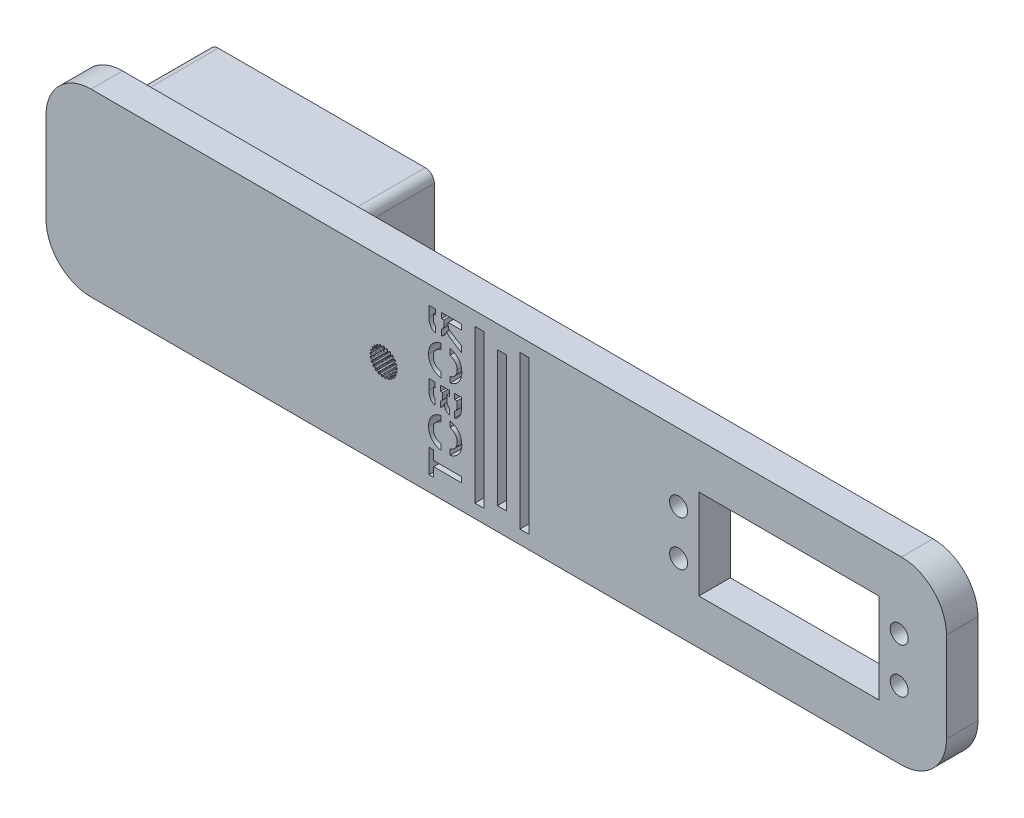
SolidWorks part; units mm, degrees
ref_plane "Alzado" through (0, 0, 0) normal (0, 0, 1) x (1, 0, 0)
ref_plane "Planta" through (0, 0, 0) normal (0, 1, 0) x (1, 0, 0)
ref_plane "Vista lateral" through (0, 0, 0) normal (1, 0, 0) x (0, 0, -1)
sketch "Croquis1" plane through (0, 0, 0) normal (0, 0, 1) x (1, 0, 0)
  line L0 (-64.25, 0) -> (10.75, 0) construction
  line L1 (0, 0) -> (0, -15.2525) construction
  line L2 (135.75, 20) -> (-64.25, 20)
  line L3 (135.75, 20) -> (135.75, -20)
  line L4 (135.75, -20) -> (-64.25, -20)
  line L5 (-64.25, 20) -> (-64.25, -20)
  line L56 (12.6265, 2.2468) -> (12.5286, 2.1823)
  line L57 (12.2759, 2.3659) -> (12.3069, 2.4789)
  line L58 (12.0088, 2.6428) -> (11.93, 2.5561)
  line L59 (11.6396, 2.6711) -> (11.6416, 2.7882)
  line L60 (11.312, 2.8728) -> (11.2572, 2.7692)
  line L61 (10.9474, 2.8084) -> (10.9201, 2.9223)
  line L62 (10.5799, 2.9223) -> (10.5526, 2.8084)
  line L63 (10.2428, 2.7692) -> (10.188, 2.8728)
  line L64 (9.8584, 2.7882) -> (9.8604, 2.6711)
  line L65 (9.57, 2.5561) -> (9.4912, 2.6428)
  line L66 (9.1931, 2.4789) -> (9.2241, 2.3659)
  line L67 (8.9714, 2.1823) -> (8.8735, 2.2468)
  line L68 (8.6255, 2.0138) -> (8.6836, 1.9121)
  line L69 (8.4846, 1.6715) -> (8.3738, 1.7095)
  line L70 (8.1914, 1.4222) -> (8.273, 1.3381)
  line L71 (8.1401, 1.0556) -> (8.0233, 1.0649)
  line L72 (7.9181, 0.7412) -> (8.0181, 0.6801)
  line L73 (7.9596, 0.3733) -> (7.8441, 0.3533)
  line L74 (7.8227, 0.0137) -> (7.9348, -0.0207)
  line L75 (7.9544, -0.3323) -> (7.8475, -0.3805)
  line L76 (7.9113, -0.7147) -> (8.0284, -0.7201)
  line L77 (8.1249, -1.0171) -> (8.0333, -1.0903)
  line L78 (8.1782, -1.3982) -> (8.293, -1.3744)
  line L79 (8.4603, -1.638) -> (8.3898, -1.7317)
  line L80 (8.6068, -1.9939) -> (8.7119, -1.9422)
  line L81 (8.9396, -2.156) -> (8.8946, -2.2642)
  line L82 (9.1699, -2.4642) -> (9.259, -2.3881)
  line L83 (9.5326, -2.5385) -> (9.516, -2.6545)
  line L84 (9.8324, -2.7798) -> (9.8997, -2.6838)
  line L85 (10.2022, -2.7615) -> (10.2149, -2.878)
  line L86 (10.5525, -2.9206) -> (10.5939, -2.811)
  line L87 (10.9061, -2.811) -> (10.9475, -2.9206)
  line L88 (11.2851, -2.878) -> (11.2978, -2.7615)
  line L89 (11.6003, -2.6838) -> (11.6676, -2.7798)
  line L90 (11.984, -2.6545) -> (11.9674, -2.5385)
  line L91 (12.241, -2.3881) -> (12.3301, -2.4642)
  line L92 (12.6054, -2.2642) -> (12.5604, -2.156)
  line L93 (12.7881, -1.9422) -> (12.8932, -1.9939)
  line L94 (13.1102, -1.7317) -> (13.0397, -1.638)
  line L95 (13.207, -1.3744) -> (13.3218, -1.3982)
  line L96 (13.4667, -1.0903) -> (13.3751, -1.0171)
  line L97 (13.4716, -0.7201) -> (13.5887, -0.7147)
  line L98 (13.6525, -0.3805) -> (13.5456, -0.3323)
  line L99 (13.5652, -0.0207) -> (13.6773, 0.0137)
  line L100 (13.6559, 0.3533) -> (13.5404, 0.3733)
  line L101 (13.4819, 0.6801) -> (13.5819, 0.7412)
  line L102 (13.4767, 1.0649) -> (13.3599, 1.0556)
  line L103 (13.227, 1.3381) -> (13.3086, 1.4222)
  line L104 (13.1262, 1.7095) -> (13.0154, 1.6715)
  line L105 (12.8164, 1.9121) -> (12.8745, 2.0138)
  line L106 (12.6265, 2.2468) -> (12.5286, 2.1823)
  line L107 (12.2759, 2.3659) -> (12.3069, 2.4789)
  line L108 (12.0088, 2.6428) -> (11.93, 2.5561)
  line L109 (11.6396, 2.6711) -> (11.6416, 2.7882)
  line L110 (11.312, 2.8728) -> (11.2572, 2.7692)
  line L111 (10.9474, 2.8084) -> (10.9201, 2.9223)
  line L112 (10.5799, 2.9223) -> (10.5526, 2.8084)
  line L113 (10.2428, 2.7692) -> (10.188, 2.8728)
  line L114 (9.8584, 2.7882) -> (9.8604, 2.6711)
  line L115 (9.57, 2.5561) -> (9.4912, 2.6428)
  line L116 (9.1931, 2.4789) -> (9.2241, 2.3659)
  line L117 (8.9714, 2.1823) -> (8.8735, 2.2468)
  line L118 (8.6255, 2.0138) -> (8.6836, 1.9121)
  line L119 (8.4846, 1.6715) -> (8.3738, 1.7095)
  line L120 (8.1914, 1.4222) -> (8.273, 1.3381)
  line L121 (8.1401, 1.0556) -> (8.0233, 1.0649)
  line L122 (7.9181, 0.7412) -> (8.0181, 0.6801)
  line L123 (7.9596, 0.3733) -> (7.8441, 0.3533)
  line L124 (7.8227, 0.0137) -> (7.9348, -0.0207)
  line L125 (7.9544, -0.3323) -> (7.8475, -0.3805)
  line L126 (7.9113, -0.7147) -> (8.0284, -0.7201)
  line L127 (8.1249, -1.0171) -> (8.0333, -1.0903)
  line L128 (8.1782, -1.3982) -> (8.293, -1.3744)
  line L129 (8.4603, -1.638) -> (8.3898, -1.7317)
  line L130 (8.6068, -1.9939) -> (8.7119, -1.9422)
  line L131 (8.9396, -2.156) -> (8.8946, -2.2642)
  line L132 (9.1699, -2.4642) -> (9.259, -2.3881)
  line L133 (9.5326, -2.5385) -> (9.516, -2.6545)
  line L134 (9.8324, -2.7798) -> (9.8997, -2.6838)
  line L135 (10.2022, -2.7615) -> (10.2149, -2.878)
  line L136 (10.5525, -2.9206) -> (10.5939, -2.811)
  line L137 (10.9061, -2.811) -> (10.9475, -2.9206)
  line L138 (11.2851, -2.878) -> (11.2978, -2.7615)
  line L139 (11.6003, -2.6838) -> (11.6676, -2.7798)
  line L140 (11.984, -2.6545) -> (11.9674, -2.5385)
  line L141 (12.241, -2.3881) -> (12.3301, -2.4642)
  line L142 (12.6054, -2.2642) -> (12.5604, -2.156)
  line L143 (12.7881, -1.9422) -> (12.8932, -1.9939)
  line L144 (13.1102, -1.7317) -> (13.0397, -1.638)
  line L145 (13.207, -1.3744) -> (13.3218, -1.3982)
  line L146 (13.4667, -1.0903) -> (13.3751, -1.0171)
  line L147 (13.4716, -0.7201) -> (13.5887, -0.7147)
  line L148 (13.6525, -0.3805) -> (13.5456, -0.3323)
  line L149 (13.5652, -0.0207) -> (13.6773, 0.0137)
  line L150 (13.6559, 0.3533) -> (13.5404, 0.3733)
  line L151 (13.4819, 0.6801) -> (13.5819, 0.7412)
  line L152 (13.4767, 1.0649) -> (13.3599, 1.0556)
  line L153 (13.227, 1.3381) -> (13.3086, 1.4222)
  line L154 (13.1262, 1.7095) -> (13.0154, 1.6715)
  line L155 (12.8164, 1.9121) -> (12.8745, 2.0138)
  arc A53 (12.8931, 2.1702) -> (12.7813, 2.2751) centre (10.75, 0) ccw
  arc A54 (12.2759, 2.3659) -> (12.5286, 2.1823) centre (12.4487, 2.3381) ccw
  arc A55 (12.2861, 2.635) -> (12.1517, 2.7088) centre (10.75, 0) ccw
  arc A56 (11.6396, 2.6711) -> (11.93, 2.5561) centre (11.8139, 2.6871) ccw
  arc A57 (11.5825, 2.9342) -> (11.434, 2.9723) centre (10.75, 0) ccw
  arc A58 (10.9474, 2.8084) -> (11.2572, 2.7692) centre (11.1122, 2.8672) ccw
  arc A59 (10.8267, 3.049) -> (10.6733, 3.049) centre (10.75, 0) ccw
  arc A60 (10.2428, 2.7692) -> (10.5526, 2.8084) centre (10.3878, 2.8672) ccw
  arc A61 (10.066, 2.9723) -> (9.9175, 2.9342) centre (10.75, 0) ccw
  arc A62 (9.57, 2.5561) -> (9.8604, 2.6711) centre (9.6861, 2.6871) ccw
  arc A63 (9.3483, 2.7088) -> (9.2139, 2.635) centre (10.75, 0) ccw
  arc A64 (8.9714, 2.1823) -> (9.2241, 2.3659) centre (9.0513, 2.3381) ccw
  arc A65 (8.7187, 2.2751) -> (8.6069, 2.1702) centre (10.75, 0) ccw
  arc A66 (8.4846, 1.6715) -> (8.6836, 1.9121) centre (8.5232, 1.8422) ccw
  arc A67 (8.2167, 1.6985) -> (8.1345, 1.569) centre (10.75, 0) ccw
  arc A68 (8.1401, 1.0556) -> (8.273, 1.3381) centre (8.135, 1.2305) ccw
  arc A69 (7.8739, 1.0151) -> (7.8265, 0.8693) centre (10.75, 0) ccw
  arc A70 (7.9596, 0.3733) -> (8.0181, 0.6801) centre (7.9112, 0.5415) ccw
  arc A71 (7.7118, 0.268) -> (7.7022, 0.1149) centre (10.75, 0) ccw
  arc A72 (7.9544, -0.3323) -> (7.9348, -0.0207) centre (7.8657, -0.1815) ccw
  arc A73 (7.7406, -0.496) -> (7.7693, -0.6466) centre (10.75, 0) ccw
  arc A74 (8.1249, -1.0171) -> (8.0284, -0.7201) centre (8.0014, -0.8931) ccw
  arc A75 (7.9585, -1.2289) -> (8.0238, -1.3676) centre (10.75, 0) ccw
  arc A76 (8.4603, -1.638) -> (8.293, -1.3744) centre (8.3099, -1.5485) ccw
  arc A77 (8.3518, -1.8845) -> (8.4495, -2.0026) centre (10.75, 0) ccw
  arc A78 (8.9396, -2.156) -> (8.7119, -1.9422) centre (8.7717, -2.1067) ccw
  arc A79 (8.8958, -2.4217) -> (9.0198, -2.5118) centre (10.75, 0) ccw
  arc A80 (9.5326, -2.5385) -> (9.259, -2.3881) centre (9.3577, -2.5325) ccw
  arc A81 (9.5563, -2.8067) -> (9.6988, -2.8631) centre (10.75, 0) ccw
  arc A82 (10.2022, -2.7615) -> (9.8997, -2.6838) centre (10.0313, -2.7992) ccw
  arc A83 (10.2918, -3.0154) -> (10.4439, -3.0346) centre (10.75, 0) ccw
  arc A84 (10.9061, -2.811) -> (10.5939, -2.811) centre (10.75, -2.89) ccw
  arc A85 (11.0561, -3.0346) -> (11.2082, -3.0154) centre (10.75, 0) ccw
  arc A86 (11.6003, -2.6838) -> (11.2978, -2.7615) centre (11.4687, -2.7992) ccw
  arc A87 (11.8012, -2.8631) -> (11.9437, -2.8067) centre (10.75, 0) ccw
  arc A88 (12.241, -2.3881) -> (11.9674, -2.5385) centre (12.1423, -2.5325) ccw
  arc A89 (12.4802, -2.5118) -> (12.6042, -2.4217) centre (10.75, 0) ccw
  arc A90 (12.7881, -1.9422) -> (12.5604, -2.156) centre (12.7283, -2.1067) ccw
  arc A91 (13.0505, -2.0026) -> (13.1482, -1.8845) centre (10.75, 0) ccw
  arc A92 (13.207, -1.3744) -> (13.0397, -1.638) centre (13.1901, -1.5485) ccw
  arc A93 (13.4762, -1.3676) -> (13.5415, -1.2289) centre (10.75, 0) ccw
  arc A94 (13.4716, -0.7201) -> (13.3751, -1.0171) centre (13.4986, -0.8931) ccw
  arc A95 (13.7307, -0.6466) -> (13.7594, -0.496) centre (10.75, 0) ccw
  arc A96 (13.5652, -0.0207) -> (13.5456, -0.3323) centre (13.6343, -0.1815) ccw
  arc A97 (13.7978, 0.1149) -> (13.7882, 0.268) centre (10.75, 0) ccw
  arc A98 (13.4819, 0.6801) -> (13.5404, 0.3733) centre (13.5888, 0.5415) ccw
  arc A99 (13.6735, 0.8693) -> (13.6261, 1.0151) centre (10.75, 0) ccw
  arc A100 (13.227, 1.3381) -> (13.3599, 1.0556) centre (13.365, 1.2305) ccw
  arc A101 (13.3655, 1.569) -> (13.2833, 1.6985) centre (10.75, 0) ccw
  arc A102 (12.8164, 1.9121) -> (13.0154, 1.6715) centre (12.9768, 1.8422) ccw
  arc A103 (12.8931, 2.1702) -> (12.7813, 2.2751) centre (10.75, 0) ccw
  arc A104 (12.2759, 2.3659) -> (12.5286, 2.1823) centre (12.4487, 2.3381) ccw
  arc A105 (12.2861, 2.635) -> (12.1517, 2.7088) centre (10.75, 0) ccw
  arc A106 (11.6396, 2.6711) -> (11.93, 2.5561) centre (11.8139, 2.6871) ccw
  arc A107 (11.5825, 2.9342) -> (11.434, 2.9723) centre (10.75, 0) ccw
  arc A108 (10.9474, 2.8084) -> (11.2572, 2.7692) centre (11.1122, 2.8672) ccw
  arc A109 (10.8267, 3.049) -> (10.6733, 3.049) centre (10.75, 0) ccw
  arc A110 (10.2428, 2.7692) -> (10.5526, 2.8084) centre (10.3878, 2.8672) ccw
  arc A111 (10.066, 2.9723) -> (9.9175, 2.9342) centre (10.75, 0) ccw
  arc A112 (9.57, 2.5561) -> (9.8604, 2.6711) centre (9.6861, 2.6871) ccw
  arc A113 (9.3483, 2.7088) -> (9.2139, 2.635) centre (10.75, 0) ccw
  arc A114 (8.9714, 2.1823) -> (9.2241, 2.3659) centre (9.0513, 2.3381) ccw
  arc A115 (8.7187, 2.2751) -> (8.6069, 2.1702) centre (10.75, 0) ccw
  arc A116 (8.4846, 1.6715) -> (8.6836, 1.9121) centre (8.5232, 1.8422) ccw
  arc A117 (8.2167, 1.6985) -> (8.1345, 1.569) centre (10.75, 0) ccw
  arc A118 (8.1401, 1.0556) -> (8.273, 1.3381) centre (8.135, 1.2305) ccw
  arc A119 (7.8739, 1.0151) -> (7.8265, 0.8693) centre (10.75, 0) ccw
  arc A120 (7.9596, 0.3733) -> (8.0181, 0.6801) centre (7.9112, 0.5415) ccw
  arc A121 (7.7118, 0.268) -> (7.7022, 0.1149) centre (10.75, 0) ccw
  arc A122 (7.9544, -0.3323) -> (7.9348, -0.0207) centre (7.8657, -0.1815) ccw
  arc A123 (7.7406, -0.496) -> (7.7693, -0.6466) centre (10.75, 0) ccw
  arc A124 (8.1249, -1.0171) -> (8.0284, -0.7201) centre (8.0014, -0.8931) ccw
  arc A125 (7.9585, -1.2289) -> (8.0238, -1.3676) centre (10.75, 0) ccw
  arc A126 (8.4603, -1.638) -> (8.293, -1.3744) centre (8.3099, -1.5485) ccw
  arc A127 (8.3518, -1.8845) -> (8.4495, -2.0026) centre (10.75, 0) ccw
  arc A128 (8.9396, -2.156) -> (8.7119, -1.9422) centre (8.7717, -2.1067) ccw
  arc A129 (8.8958, -2.4217) -> (9.0198, -2.5118) centre (10.75, 0) ccw
  arc A130 (9.5326, -2.5385) -> (9.259, -2.3881) centre (9.3577, -2.5325) ccw
  arc A131 (9.5563, -2.8067) -> (9.6988, -2.8631) centre (10.75, 0) ccw
  arc A132 (10.2022, -2.7615) -> (9.8997, -2.6838) centre (10.0313, -2.7992) ccw
  arc A133 (10.2918, -3.0154) -> (10.4439, -3.0346) centre (10.75, 0) ccw
  arc A134 (10.9061, -2.811) -> (10.5939, -2.811) centre (10.75, -2.89) ccw
  arc A135 (11.0561, -3.0346) -> (11.2082, -3.0154) centre (10.75, 0) ccw
  arc A136 (11.6003, -2.6838) -> (11.2978, -2.7615) centre (11.4687, -2.7992) ccw
  arc A137 (11.8012, -2.8631) -> (11.9437, -2.8067) centre (10.75, 0) ccw
  arc A138 (12.241, -2.3881) -> (11.9674, -2.5385) centre (12.1423, -2.5325) ccw
  arc A139 (12.4802, -2.5118) -> (12.6042, -2.4217) centre (10.75, 0) ccw
  arc A140 (12.7881, -1.9422) -> (12.5604, -2.156) centre (12.7283, -2.1067) ccw
  arc A141 (13.0505, -2.0026) -> (13.1482, -1.8845) centre (10.75, 0) ccw
  arc A142 (13.207, -1.3744) -> (13.0397, -1.638) centre (13.1901, -1.5485) ccw
  arc A143 (13.4762, -1.3676) -> (13.5415, -1.2289) centre (10.75, 0) ccw
  arc A144 (13.4716, -0.7201) -> (13.3751, -1.0171) centre (13.4986, -0.8931) ccw
  arc A145 (13.7307, -0.6466) -> (13.7594, -0.496) centre (10.75, 0) ccw
  arc A146 (13.5652, -0.0207) -> (13.5456, -0.3323) centre (13.6343, -0.1815) ccw
  arc A147 (13.7978, 0.1149) -> (13.7882, 0.268) centre (10.75, 0) ccw
  arc A148 (13.4819, 0.6801) -> (13.5404, 0.3733) centre (13.5888, 0.5415) ccw
  arc A149 (13.6735, 0.8693) -> (13.6261, 1.0151) centre (10.75, 0) ccw
  arc A150 (13.227, 1.3381) -> (13.3599, 1.0556) centre (13.365, 1.2305) ccw
  arc A151 (13.3655, 1.569) -> (13.2833, 1.6985) centre (10.75, 0) ccw
  arc A152 (12.8164, 1.9121) -> (13.0154, 1.6715) centre (12.9768, 1.8422) ccw
  spline S50 degree 3 poles (5991.9772, -495.1912) (-77.9359, 29.7028) (12.0665, -1.5466) (12.9076, 2.1011) (12.9095, 2.115) (12.8341, 3.4331) (-11.0318, 17.2816) (-3713.5828, -4698.8555) knots -68.19884 -68.19884 -68.19884 -68.19884 0.5 0.5 0.75 0.75 23.694066 23.694066 23.694066 23.694066 only from (12.8745, 2.0138) to (12.8931, 2.1702)
  spline S51 degree 3 poles (-4350.7805, -4114.6425) (28.1487, -21.0181) (14.0631, 2.2949) (12.7252, 2.2881) (12.7115, 2.2853) (9.1534, 1.2271) (43.9396, -86.0291) (-459.254, 5983.3688) knots -22.897234 -22.897234 -22.897234 -22.897234 0.25 0.25 0.5 0.5 68.630064 68.630064 68.630064 68.630064 only from (12.7813, 2.2751) to (12.6265, 2.2468)
  spline S52 degree 3 poles (5927.215, 1007.8369) (-82.5365, 6.7143) (12.4097, -1.1707) (12.3173, 2.5717) (12.3157, 2.5856) (11.9148, 3.8436) (-14.6453, 11.3217) (-2428.0182, -5477.4362) knots -68.19884 -68.19884 -68.19884 -68.19884 0.5 0.5 0.75 0.75 23.694066 23.694066 23.694066 23.694066 only from (12.3069, 2.4789) to (12.2861, 2.635)
  spline S53 degree 3 poles (-3190.485, -5070.042) (32.8291, -16.0309) (13.3883, 3.0468) (12.0941, 2.7074) (12.0816, 2.7013) (8.8984, 0.7915) (64.2914, -75.0724) (-1932.4913, 5678.5051) knots -22.897234 -22.897234 -22.897234 -22.897234 0.25 0.25 0.5 0.5 68.630064 68.630064 68.630064 68.630064 only from (12.1517, 2.7088) to (12.0088, 2.6428)
  spline S54 degree 3 poles (5490.6996, 2447.5389) (-81.2755, -16.696) (12.6487, -0.7211) (11.6285, 2.8806) (11.6235, 2.8938) (10.9224, 4.0125) (-16.663, 4.6505) (-989.2168, -5911.8495) knots -68.19884 -68.19884 -68.19884 -68.19884 0.5 0.5 0.75 0.75 23.694066 23.694066 23.694066 23.694066 only from (11.6416, 2.7882) to (11.5825, 2.9342)
  spline S55 degree 3 poles (-1829.0442, -5706.8721) (36.1221, -10.0364) (12.5477, 3.6072) (11.3786, 2.9566) (11.368, 2.9476) (8.7597, 0.3062) (81.2791, -59.3987) (-3283.6276, 5016.8399) knots -22.897234 -22.897234 -22.897234 -22.897234 0.25 0.25 0.5 0.5 68.630064 68.630064 68.630064 68.630064 only from (11.434, 2.9723) to (11.312, 2.8728)
  spline S56 degree 3 poles (4709.8587, 3733.453) (-74.2322, -39.0573) (12.7684, -0.2263) (10.8845, 3.0086) (10.8764, 3.0201) (9.9191, 3.9293) (-16.9583, -2.3129) (512.4161, -5974.7995) knots -68.19884 -68.19884 -68.19884 -68.19884 0.5 0.5 0.75 0.75 23.694066 23.694066 23.694066 23.694066 only from (10.9201, 2.9223) to (10.8267, 3.049)
  spline S57 degree 3 poles (-352.0023, -5985.1184) (37.821, -3.4113) (11.5942, 3.9409) (10.6236, 3.0201) (10.6155, 3.0087) (8.7461, -0.1984) (93.8351, -39.9927) (-4427.766, 4039.9483) knots -22.897234 -22.897234 -22.897234 -22.897234 0.25 0.25 0.5 0.5 68.630064 68.630064 68.630064 68.630064 only from (10.6733, 3.049) to (10.5799, 2.9223)
  spline S58 degree 3 poles (3633.7556, 4784.7805) (-61.8492, -58.9645) (12.7613, 0.2828) (10.1321, 2.9476) (10.1214, 2.9566) (8.968, 3.5992) (-15.5126, -9.1311) (1982.5276, -5662.3309) knots -68.19884 -68.19884 -68.19884 -68.19884 0.5 0.5 0.75 0.75 23.694066 23.694066 23.694066 23.694066 only from (10.188, 2.8728) to (10.066, 2.9723)
  spline S59 degree 3 poles (1147.8327, -5887.2977) (37.8188, 3.4281) (10.5876, 4.0271) (9.8765, 2.8938) (9.8715, 2.8807) (8.8584, -0.6905) (101.1706, -18.0738) (-5293.0161, 2809.2118) knots -22.897234 -22.897234 -22.897234 -22.897234 0.25 0.25 0.5 0.5 68.630064 68.630064 68.630064 68.630064 only from (9.9175, 2.9342) to (9.8584, 2.7882)
  spline S60 degree 3 poles (2330.0056, 5535.4627) (-44.9045, -75.1667) (12.6278, 0.7741) (9.4185, 2.7013) (9.4058, 2.7074) (8.1289, 3.043) (-12.4167, -15.3754) (3328.745, -4994.0772) knots -68.19884 -68.19884 -68.19884 -68.19884 0.5 0.5 0.75 0.75 23.694066 23.694066 23.694066 23.694066 only from (9.4912, 2.6428) to (9.3483, 2.7088)
  spline S61 degree 3 poles (2576.2205, -5419.5565) (36.1159, 10.0522) (9.5912, 3.8602) (9.1843, 2.5856) (9.1827, 2.5717) (9.0895, -1.1392) (102.8246, 4.9807) (-5825.0111, 1401.9623) knots -22.897234 -22.897234 -22.897234 -22.897234 0.25 0.25 0.5 0.5 68.630064 68.630064 68.630064 68.630064 only from (9.2139, 2.635) to (9.1931, 2.4789)
  spline S62 degree 3 poles (880.5284, 5938.3314) (-24.4628, -86.6459) (12.3763, 1.2167) (8.7885, 2.2853) (8.7748, 2.2881) (7.4545, 2.2955) (-7.8652, -20.6537) (4466.4806, -4012.0273) knots -68.19884 -68.19884 -68.19884 -68.19884 0.5 0.5 0.75 0.75 23.694066 23.694066 23.694066 23.694066 only from (8.8735, 2.2468) to (8.7187, 2.2751)
  spline S63 degree 3 poles (3843.4104, -4611.2846) (32.8191, 16.0446) (8.6676, 3.4507) (8.5904, 2.115) (8.5924, 2.1012) (9.425, -1.5164) (98.6933, 27.7223) (-5990.3238, -93.3777) knots -22.897234 -22.897234 -22.897234 -22.897234 0.25 0.25 0.5 0.5 68.630064 68.630064 68.630064 68.630064 only from (8.6069, 2.1702) to (8.6255, 2.0138)
  spline S64 degree 3 poles (-623.6003, 5968.0728) (-1.8086, -92.6808) (12.0226, 1.583) (8.2818, 1.7257) (8.2678, 1.725) (6.9872, 1.4038) (-2.144, -24.6343) (5324.2462, -2777.8869) knots -68.19884 -68.19884 -68.19884 -68.19884 0.5 0.5 0.75 0.75 23.694066 23.694066 23.694066 23.694066 only from (8.3738, 1.7095) to (8.2167, 1.6985)
  spline S65 degree 3 poles (4869.7802, -3513.2687) (28.1356, 21.0289) (7.8749, 2.8244) (8.1323, 1.5115) (8.1376, 1.4986) (9.8438, -1.7982) (89.0362, 48.7219) (-5778.5669, -1582.8504) knots -22.897234 -22.897234 -22.897234 -22.897234 0.25 0.25 0.5 0.5 68.630064 68.630064 68.630064 68.630064 only from (8.1345, 1.569) to (8.1914, 1.4222)
  spline S66 degree 3 poles (-2087.8703, 5622.8184) (21.6348, -92.8922) (11.5889, 1.8497) (7.9302, 1.0577) (7.9168, 1.0535) (6.7563, 0.424) (4.3874, -27.0669) (5848.1454, -1369.2017) knots -68.19884 -68.19884 -68.19884 -68.19884 0.5 0.5 0.75 0.75 23.694066 23.694066 23.694066 23.694066 only from (8.0233, 1.0649) to (7.8739, 1.0151)
  spline S67 degree 3 poles (5590.8392, -2194.5012) (22.3597, 24.6919) (7.2628, 2.0207) (7.8387, 0.813) (7.847, 0.8018) (10.3194, -1.9671) (74.46, 66.6602) (-5203.046, -2972.8669) knots -22.897234 -22.897234 -22.897234 -22.897234 0.25 0.25 0.5 0.5 68.630064 68.630064 68.630064 68.630064 only from (7.8265, 0.8693) to (7.9181, 0.7412)
  spline S68 degree 3 poles (-3420.2764, 4924.2615) (44.3942, -87.2669) (11.1026, 2.0002) (7.7558, 0.3232) (7.7438, 0.3158) (6.7763, -0.5826) (11.3186, -27.7989) (6005.2595, 125.5155) knots -68.19884 -68.19884 -68.19884 -68.19884 0.5 0.5 0.75 0.75 23.694066 23.694066 23.694066 23.694066 only from (7.8441, 0.3533) to (7.7118, 0.268)
  spline S69 degree 3 poles (5961.2807, -737.8452) (15.8544, 26.8034) (6.8699, 1.09) (7.7279, 0.0635) (7.7388, 0.0547) (10.8222, -2.0124) (55.8807, 80.41) (-4299.9231, -4176.0871) knots -22.897234 -22.897234 -22.897234 -22.897234 0.25 0.25 0.5 0.5 68.630064 68.630064 68.630064 68.630064 only from (7.7022, 0.1149) to (7.8227, 0.0137)
  spline S70 degree 3 poles (-4537.0984, 3916.2952) (65.0396, -76.1583) (10.5941, 2.0251) (7.7695, -0.4316) (7.7597, -0.4417) (7.046, -1.5525) (18.214, -26.7841) (5785.7165, 1612.3461) knots -68.19884 -68.19884 -68.19884 -68.19884 0.5 0.5 0.75 0.75 23.694066 23.694066 23.694066 23.694066 only from (7.8475, -0.3805) to (7.7406, -0.496)
  spline S71 degree 3 poles (5957.8285, 765.1724) (9.0283, 27.2307) (6.7207, 0.0908) (7.8071, -0.6901) (7.8198, -0.6959) (11.3204, -1.9312) (34.4657, 89.1073) (-3125.9447, -5116.9085) knots -22.897234 -22.897234 -22.897234 -22.897234 0.25 0.25 0.5 0.5 68.630064 68.630064 68.630064 68.630064 only from (7.7693, -0.6466) to (7.9113, -0.7147)
  spline S72 degree 3 poles (-5368.1624, 2662.2537) (82.2738, -60.2644) (10.0953, 1.9227) (7.9704, -1.1593) (7.9635, -1.1715) (7.5485, -2.4248) (24.6405, -24.0864) (5203.3112, 2997.867) knots -68.19884 -68.19884 -68.19884 -68.19884 0.5 0.5 0.75 0.75 23.694066 23.694066 23.694066 23.694066 only from (8.0333, -1.0903) to (7.9585, -1.2289)
  spline S73 degree 3 poles (5580.6995, 2220.1114) (2.3104, 25.947) (6.8247, -0.9141) (8.0712, -1.4003) (8.0849, -1.4027) (11.7827, -1.7287) (11.5605, 92.2057) (-1754.8763, -5736.2156) knots -22.897234 -22.897234 -22.897234 -22.897234 0.25 0.25 0.5 0.5 68.630064 68.630064 68.630064 68.630064 only from (8.0238, -1.3676) to (8.1782, -1.3982)
  spline S74 degree 3 poles (-5861.2496, 1240.933) (95.0139, -40.5839) (9.6378, 1.6994) (8.3461, -1.8141) (8.3424, -1.8277) (8.2521, -3.1449) (30.1941, -19.8753) (4294.6381, 4195.021) knots -68.19884 -68.19884 -68.19884 -68.19884 0.5 0.5 0.75 0.75 23.694066 23.694066 23.694066 23.694066 only from (8.3898, -1.7317) to (8.3518, -1.8845)
  spline S75 degree 3 poles (4853.59, 3535.5526) (-3.8772, 23.033) (7.1754, -1.8616) (8.5036, -2.0225) (8.5175, -2.0214) (12.1802, -1.4176) (-11.3955, 89.5105) (-272.8671, -5995.0953) knots -22.897234 -22.897234 -22.897234 -22.897234 0.25 0.25 0.5 0.5 68.630064 68.630064 68.630064 68.630064 only from (8.4495, -2.0026) to (8.6068, -1.9939)
  spline S76 degree 3 poles (-5985.3774, -258.3601) (102.4594, -18.3533) (9.2501, 1.3695) (8.8727, -2.3549) (8.8726, -2.369) (9.1127, -3.6673) (34.526, -14.4153) (3116.7926, 5128.5863) knots -68.19884 -68.19884 -68.19884 -68.19884 0.5 0.5 0.75 0.75 23.694066 23.694066 23.694066 23.694066 only from (8.8946, -2.2642) to (8.8958, -2.4217)
  spline S77 degree 3 poles (3822.1871, 4628.8421) (-9.1458, 18.6717) (7.7506, -2.6921) (9.0771, -2.5176) (9.0903, -2.5131) (12.4878, -1.0174) (-32.9602, 81.191) (1226.9628, -5877.2811) knots -22.897234 -22.897234 -22.897234 -22.897234 0.25 0.25 0.5 0.5 68.630064 68.630064 68.630064 68.630064 only from (9.0198, -2.5118) to (9.1699, -2.4642)
  spline S78 degree 3 poles (-5732.7465, -1741.4195) (104.1424, 5.0305) (8.9566, 0.9534) (9.5174, -2.7478) (9.5207, -2.7615) (10.0761, -3.9592) (37.364, -8.0496) (1743.783, 5739.9037) knots -68.19884 -68.19884 -68.19884 -68.19884 0.5 0.5 0.75 0.75 23.694066 23.694066 23.694066 23.694066 only from (9.516, -2.6545) to (9.5563, -2.8067)
  spline S79 degree 3 poles (2551.2976, 5431.2843) (-13.1642, 13.1373) (8.5143, -3.3534) (9.7558, -2.8545) (9.7675, -2.8469) (12.6862, -0.5532) (-51.7783, 67.7699) (2650.3736, -5390.1756) knots -22.897234 -22.897234 -22.897234 -22.897234 0.25 0.25 0.5 0.5 68.630064 68.630064 68.630064 68.630064 only from (9.6988, -2.8631) to (9.8324, -2.7798)
  spline S80 degree 3 poles (-5119.2306, -3115.0591) (99.9573, 28.0982) (8.7759, 0.4775) (10.2394, -2.968) (10.2461, -2.9804) (11.0819, -4.0024) (38.5297, -1.1781) (261.8806, 5990.5619) knots -68.19884 -68.19884 -68.19884 -68.19884 0.5 0.5 0.75 0.75 23.694066 23.694066 23.694066 23.694066 only from (10.2149, -2.878) to (10.2918, -3.0154)
  spline S81 degree 3 poles (1120.7761, 5892.459) (-15.68, 6.7773) (9.4185, -3.804) (10.4969, -3.0121) (10.5063, -3.0018) (12.763, -0.0543) (-66.6675, 50.0906) (3907.9272, -4564.3856) knots -22.897234 -22.897234 -22.897234 -22.897234 0.25 0.25 0.5 0.5 68.630064 68.630064 68.630064 68.630064 only from (10.4439, -3.0346) to (10.5525, -2.9206)
  spline S82 degree 3 poles (-4183.3791, -4292.9681) (90.1669, 49.4004) (8.7191, -0.0285) (10.9936, -3.0018) (11.0031, -3.0121) (12.0668, -3.7942) (37.95, 5.7675) (-1235.8013, 5864.811) knots -68.19884 -68.19884 -68.19884 -68.19884 0.5 0.5 0.75 0.75 23.694066 23.694066 23.694066 23.694066 only from (10.9475, -2.9206) to (11.0561, -3.0346)
  spline S83 degree 3 poles (-379.4924, 5983.3889) (-16.5351, -0.0085) (10.4064, -4.0157) (11.2539, -2.9804) (11.2605, -2.9681) (12.7132, 0.448) (-76.6924, 29.264) (4920.6067, -3451.7985) knots -22.897234 -22.897234 -22.897234 -22.897234 0.25 0.25 0.5 0.5 68.630064 68.630064 68.630064 68.630064 only from (11.2082, -3.0154) to (11.2851, -2.878)
  spline S84 degree 3 poles (-2983.9951, -5201.1341) (75.3865, 67.5986) (8.79, -0.5326) (11.7325, -2.8469) (11.7442, -2.8545) (12.969, -3.3475) (35.6611, 12.3506) (-2655.1578, 5370.5525) knots -68.19884 -68.19884 -68.19884 -68.19884 0.5 0.5 0.75 0.75 23.694066 23.694066 23.694066 23.694066 only from (11.6676, -2.7798) to (11.8012, -2.8631)
  spline S85 degree 3 poles (-1855.2405, 5698.3604) (-15.6757, -6.7937) (11.4158, -3.9749) (11.9793, -2.7615) (11.9826, -2.7479) (12.5401, 0.9221) (-81.2229, 6.5986) (5624.7819, -2122.3222) knots -22.897234 -22.897234 -22.897234 -22.897234 0.25 0.25 0.5 0.5 68.630064 68.630064 68.630064 68.630064 only from (11.9437, -2.8067) to (11.984, -2.6545)
  spline S86 degree 3 poles (-1596.4402, -5782.4937) (56.5447, 81.5493) (8.9841, -1.0033) (12.4096, -2.5131) (12.4229, -2.5176) (13.7318, -2.6905) (31.807, 18.1578) (-3907.0055, 4538.8424) knots -68.19884 -68.19884 -68.19884 -68.19884 0.5 0.5 0.75 0.75 23.694066 23.694066 23.694066 23.694066 only from (12.3301, -2.4642) to (12.4802, -2.5118)
  spline S87 degree 3 poles (-3213.7416, 5055.283) (-13.156, -13.1521) (12.3835, -3.6845) (12.6274, -2.369) (12.6273, -2.355) (12.2546, 1.3384) (-79.9744, -16.4814) (5976.2069, -659.4926) knots -22.897234 -22.897234 -22.897234 -22.897234 0.25 0.25 0.5 0.5 68.630064 68.630064 68.630064 68.630064 only from (12.6042, -2.4217) to (12.6054, -2.2642)
  spline S88 degree 3 poles (-107.8996, -6000.518) (34.8255, 90.376) (9.2891, -1.411) (12.9824, -2.0214) (12.9964, -2.0225) (14.3072, -1.8644) (26.6298, 22.824) (-4912.6862, 3421.9401) knots -68.19884 -68.19884 -68.19884 -68.19884 0.5 0.5 0.75 0.75 23.694066 23.694066 23.694066 23.694066 only from (12.8932, -1.9939) to (13.0505, -2.0026)
  spline S89 degree 3 poles (-4369.636, 4094.5635) (-9.1342, -18.6841) (13.2484, -3.1625) (13.1576, -1.8277) (13.154, -1.8142) (11.8745, 1.6705) (-73.0253, -38.5259) (5952.8002, 844.7754) knots -22.897234 -22.897234 -22.897234 -22.897234 0.25 0.25 0.5 0.5 68.630064 68.630064 68.630064 68.630064 only from (13.1482, -1.8845) to (13.1102, -1.7317)
  spline S90 degree 3 poles (1388.0961, -5841.5076) (11.5936, 93.524) (9.6859, -1.73) (13.415, -1.4027) (13.4288, -1.4003) (14.6591, -0.9212) (20.4548, 26.0561) (-5609.0093, 2090.0248) knots -68.19884 -68.19884 -68.19884 -68.19884 0.5 0.5 0.75 0.75 23.694066 23.694066 23.694066 23.694066 only from (13.3218, -1.3982) to (13.4762, -1.3676)
  spline S91 degree 3 poles (-5250.2946, 2876.5676) (-3.8629, -23.0421) (13.9564, -2.4418) (13.5365, -1.1715) (13.5296, -1.1593) (11.4237, 1.8976) (-60.8124, -58.1496) (5556.0327, 2295.963) knots -22.897234 -22.897234 -22.897234 -22.897234 0.25 0.25 0.5 0.5 68.630064 68.630064 68.630064 68.630064 only from (13.5415, -1.2289) to (13.4667, -1.0903)
  spline S92 degree 3 poles (2797.5481, -5315.4539) (-11.6914, 90.7955) (10.1495, -1.9403) (13.6801, -0.6959) (13.6929, -0.6901) (14.7654, 0.0799) (13.67, 27.6509) (-5952.2223, 626.7855) knots -68.19884 -68.19884 -68.19884 -68.19884 0.5 0.5 0.75 0.75 23.694066 23.694066 23.694066 23.694066 only from (13.5887, -0.7147) to (13.7307, -0.6466)
  spline S93 degree 3 poles (-5800.3825, 1477.8263) (2.3265, -25.9523) (14.4629, -1.5677) (13.7403, -0.4417) (13.7306, -0.4317) (10.9306, 2.0056) (-44.1029, -74.1196) (4810.8347, 3602.8868) knots -22.897234 -22.897234 -22.897234 -22.897234 0.25 0.25 0.5 0.5 68.630064 68.630064 68.630064 68.630064 only from (13.7594, -0.496) to (13.6525, -0.3805)
  spline S94 degree 3 poles (4031.8953, -4455.4106) (-33.5663, 82.3621) (10.6509, -2.0286) (13.7611, 0.0546) (13.7721, 0.0635) (14.6194, 1.076) (6.7018, 27.5084) (-5920.7597, -875.837) knots -68.19884 -68.19884 -68.19884 -68.19884 0.5 0.5 0.75 0.75 23.694066 23.694066 23.694066 23.694066 only from (13.6773, 0.0137) to (13.7978, 0.1149)
  spline S95 degree 3 poles (-5985.3355, -13.7722) (9.0452, -27.2318) (14.7362, -0.5951) (13.7562, 0.3158) (13.7443, 0.3231) (10.4262, 1.9875) (-23.9468, -85.4323) (3764.0296, 4683.428) knots -22.897234 -22.897234 -22.897234 -22.897234 0.25 0.25 0.5 0.5 68.630064 68.630064 68.630064 68.630064 only from (13.7882, 0.268) to (13.6559, 0.3533)
  spline S96 degree 3 poles (5013.5792, -3315.4175) (-52.6566, 68.7535) (11.1585, -1.9895) (13.6529, 0.8018) (13.6613, 0.813) (14.2302, 2.0045) (-0.0121, 25.6375) (-5516.5986, -2323.4274) knots -68.19884 -68.19884 -68.19884 -68.19884 0.5 0.5 0.75 0.75 23.694066 23.694066 23.694066 23.694066 only from (13.5819, 0.7412) to (13.6735, 0.8693)
  spline S97 degree 3 poles (-5793.5325, -1504.5054) (15.871, -26.8002) (14.7589, 0.4149) (13.5832, 1.0535) (13.5699, 1.0577) (9.9421, 1.8445) (-1.6106, -91.377) (2481.3923, 5469.6922) knots -22.897234 -22.897234 -22.897234 -22.897234 0.25 0.25 0.5 0.5 68.630064 68.630064 68.630064 68.630064 only from (13.6261, 1.0151) to (13.4767, 1.0649)
  spline S98 degree 3 poles (5680.917, -1967.1046) (-67.7629, 50.8249) (11.6405, -1.8254) (13.3624, 1.4985) (13.3677, 1.5115) (13.6224, 2.807) (-6.0498, 22.1556) (-4765.1339, -3625.0284) knots -68.19884 -68.19884 -68.19884 -68.19884 0.5 0.5 0.75 0.75 23.694066 23.694066 23.694066 23.694066 only from (13.3086, 1.4222) to (13.3655, 1.569)
  spline S99 degree 3 poles (-5237.025, -2900.7049) (22.3751, -24.6847) (14.5298, 1.3989) (13.2322, 1.725) (13.2183, 1.7257) (9.5088, 1.5856) (21.5023, -91.5802) (1043.5154, 5912.2755) knots -22.897234 -22.897234 -22.897234 -22.897234 0.25 0.25 0.5 0.5 68.630064 68.630064 68.630064 68.630064 only from (13.2833, 1.6985) to (13.1262, 1.7095)
  spline S100 degree 3 poles (12.8745, 2.0138) (12.8876, 2.0368) (12.8985, 2.0614) (12.9076, 2.1011) (12.9095, 2.115) (12.9079, 2.1434) (12.9043, 2.1591) (12.8931, 2.1702) knots 0 0 0 0 0.5 0.5 0.75 0.75 1 1 1 1
  spline S101 degree 3 poles (12.7813, 2.2751) (12.7696, 2.2856) (12.7538, 2.2882) (12.7252, 2.2881) (12.7115, 2.2853) (12.6725, 2.2737) (12.6486, 2.2613) (12.6265, 2.2468) knots 0 0 0 0 0.25 0.25 0.5 0.5 1 1 1 1
  spline S102 degree 3 poles (12.3069, 2.4789) (12.314, 2.5044) (12.3183, 2.531) (12.3173, 2.5717) (12.3157, 2.5856) (12.3071, 2.6127) (12.2996, 2.627) (12.2861, 2.635) knots 0 0 0 0 0.5 0.5 0.75 0.75 1 1 1 1
  spline S103 degree 3 poles (12.1517, 2.7088) (12.1378, 2.716) (12.1218, 2.7147) (12.0941, 2.7074) (12.0816, 2.7013) (12.0467, 2.6804) (12.0266, 2.6624) (12.0088, 2.6428) knots 0 0 0 0 0.25 0.25 0.5 0.5 1 1 1 1
  spline S104 degree 3 poles (11.6416, 2.7882) (11.642, 2.8147) (11.6396, 2.8415) (11.6285, 2.8806) (11.6235, 2.8938) (11.6084, 2.9179) (11.5976, 2.9299) (11.5825, 2.9342) knots 0 0 0 0 0.5 0.5 0.75 0.75 1 1 1 1
  spline S105 degree 3 poles (11.434, 2.9723) (11.4187, 2.9758) (11.4036, 2.9705) (11.3786, 2.9566) (11.368, 2.9476) (11.3394, 2.9186) (11.3243, 2.8963) (11.312, 2.8728) knots 0 0 0 0 0.25 0.25 0.5 0.5 1 1 1 1
  spline S106 degree 3 poles (10.9201, 2.9223) (10.914, 2.9481) (10.905, 2.9734) (10.8845, 3.0086) (10.8764, 3.0201) (10.8558, 3.0397) (10.8424, 3.0486) (10.8267, 3.049) knots 0 0 0 0 0.5 0.5 0.75 0.75 1 1 1 1
  spline S107 degree 3 poles (10.6733, 3.049) (10.6576, 3.0486) (10.6443, 3.0398) (10.6236, 3.0201) (10.6155, 3.0087) (10.595, 2.9735) (10.586, 2.9481) (10.5799, 2.9223) knots 0 0 0 0 0.25 0.25 0.5 0.5 1 1 1 1
  spline S108 degree 3 poles (10.188, 2.8728) (10.1757, 2.8963) (10.1607, 2.9186) (10.1321, 2.9476) (10.1214, 2.9566) (10.0965, 2.9705) (10.0813, 2.9758) (10.066, 2.9723) knots 0 0 0 0 0.5 0.5 0.75 0.75 1 1 1 1
  spline S109 degree 3 poles (9.9175, 2.9342) (9.9024, 2.9299) (9.8917, 2.918) (9.8765, 2.8938) (9.8715, 2.8807) (9.8604, 2.8415) (9.858, 2.8147) (9.8584, 2.7882) knots 0 0 0 0 0.25 0.25 0.5 0.5 1 1 1 1
  spline S110 degree 3 poles (9.4912, 2.6428) (9.4734, 2.6624) (9.4534, 2.6803) (9.4185, 2.7013) (9.4058, 2.7074) (9.3783, 2.7147) (9.3623, 2.716) (9.3483, 2.7088) knots 0 0 0 0 0.5 0.5 0.75 0.75 1 1 1 1
  spline S111 degree 3 poles (9.2139, 2.635) (9.2004, 2.627) (9.193, 2.6129) (9.1843, 2.5856) (9.1827, 2.5717) (9.1817, 2.531) (9.186, 2.5044) (9.1931, 2.4789) knots 0 0 0 0 0.25 0.25 0.5 0.5 1 1 1 1
  spline S112 degree 3 poles (8.8735, 2.2468) (8.8514, 2.2613) (8.8276, 2.2737) (8.7885, 2.2853) (8.7748, 2.2881) (8.7463, 2.2882) (8.7304, 2.2856) (8.7187, 2.2751) knots 0 0 0 0 0.5 0.5 0.75 0.75 1 1 1 1
  spline S113 degree 3 poles (8.6069, 2.1702) (8.5957, 2.1591) (8.5921, 2.1435) (8.5904, 2.115) (8.5924, 2.1012) (8.6015, 2.0615) (8.6124, 2.0368) (8.6255, 2.0138) knots 0 0 0 0 0.25 0.25 0.5 0.5 1 1 1 1
  spline S114 degree 3 poles (8.3738, 1.7095) (8.3487, 1.7181) (8.3225, 1.7241) (8.2818, 1.7257) (8.2678, 1.725) (8.2402, 1.7181) (8.2254, 1.7115) (8.2167, 1.6985) knots 0 0 0 0 0.5 0.5 0.75 0.75 1 1 1 1
  spline S115 degree 3 poles (8.1345, 1.569) (8.1265, 1.5556) (8.1268, 1.5396) (8.1323, 1.5115) (8.1376, 1.4986) (8.1563, 1.4624) (8.173, 1.4412) (8.1914, 1.4222) knots 0 0 0 0 0.25 0.25 0.5 0.5 1 1 1 1
  spline S116 degree 3 poles (8.0233, 1.0649) (7.9969, 1.067) (7.97, 1.0663) (7.9302, 1.0577) (7.9168, 1.0535) (7.8918, 1.0399) (7.8791, 1.0299) (7.8739, 1.0151) knots 0 0 0 0 0.5 0.5 0.75 0.75 1 1 1 1
  spline S117 degree 3 poles (7.8265, 0.8693) (7.822, 0.8542) (7.8264, 0.8388) (7.8387, 0.813) (7.847, 0.8018) (7.8741, 0.7715) (7.8955, 0.7551) (7.9181, 0.7412) knots 0 0 0 0 0.25 0.25 0.5 0.5 1 1 1 1
  spline S118 degree 3 poles (7.8441, 0.3533) (7.818, 0.3488) (7.7922, 0.3414) (7.7558, 0.3232) (7.7438, 0.3158) (7.723, 0.2964) (7.7132, 0.2836) (7.7118, 0.268) knots 0 0 0 0 0.5 0.5 0.75 0.75 1 1 1 1
  spline S119 degree 3 poles (7.7022, 0.1149) (7.7016, 0.0992) (7.7096, 0.0854) (7.7279, 0.0635) (7.7388, 0.0547) (7.7726, 0.032) (7.7974, 0.0214) (7.8227, 0.0137) knots 0 0 0 0 0.25 0.25 0.5 0.5 1 1 1 1
  spline S120 degree 3 poles (7.8475, -0.3805) (7.8234, -0.3913) (7.8002, -0.4049) (7.7695, -0.4316) (7.7597, -0.4417) (7.7443, -0.4657) (7.738, -0.4805) (7.7406, -0.496) knots 0 0 0 0 0.5 0.5 0.75 0.75 1 1 1 1
  spline S121 degree 3 poles (7.7693, -0.6466) (7.7727, -0.662) (7.7839, -0.6734) (7.8071, -0.6901) (7.8198, -0.6959) (7.8582, -0.7094) (7.8849, -0.7135) (7.9113, -0.7147) knots 0 0 0 0 0.25 0.25 0.5 0.5 1 1 1 1
  spline S122 degree 3 poles (8.0333, -1.0903) (8.0127, -1.1069) (7.9935, -1.1257) (7.9704, -1.1593) (7.9635, -1.1715) (7.9546, -1.1985) (7.9522, -1.2145) (7.9585, -1.2289) knots 0 0 0 0 0.5 0.5 0.75 0.75 1 1 1 1
  spline S123 degree 3 poles (8.0238, -1.3676) (8.0308, -1.3816) (8.0445, -1.3899) (8.0712, -1.4003) (8.0849, -1.4027) (8.1255, -1.4063) (8.1523, -1.4036) (8.1782, -1.3982) knots 0 0 0 0 0.25 0.25 0.5 0.5 1 1 1 1
  spline S124 degree 3 poles (8.3898, -1.7317) (8.3739, -1.7528) (8.3601, -1.7759) (8.3461, -1.8141) (8.3424, -1.8277) (8.3405, -1.8561) (8.3421, -1.8721) (8.3518, -1.8845) knots 0 0 0 0 0.5 0.5 0.75 0.75 1 1 1 1
  spline S125 degree 3 poles (8.4495, -2.0026) (8.4599, -2.0144) (8.4752, -2.0191) (8.5036, -2.0225) (8.5175, -2.0214) (8.5577, -2.0148) (8.583, -2.0055) (8.6068, -1.9939) knots 0 0 0 0 0.25 0.25 0.5 0.5 1 1 1 1
  spline S126 degree 3 poles (8.8946, -2.2642) (8.8845, -2.2887) (8.8768, -2.3144) (8.8727, -2.3549) (8.8726, -2.369) (8.8777, -2.397) (8.8833, -2.4121) (8.8958, -2.4217) knots 0 0 0 0 0.5 0.5 0.75 0.75 1 1 1 1
  spline S127 degree 3 poles (9.0198, -2.5118) (9.0328, -2.5207) (9.0488, -2.5213) (9.0771, -2.5176) (9.0903, -2.5131) (9.1276, -2.4967) (9.1498, -2.4814) (9.1699, -2.4642) knots 0 0 0 0 0.25 0.25 0.5 0.5 1 1 1 1
  spline S128 degree 3 poles (9.516, -2.6545) (9.5123, -2.6807) (9.5113, -2.7076) (9.5174, -2.7478) (9.5207, -2.7615) (9.5327, -2.7873) (9.5418, -2.8005) (9.5563, -2.8067) knots 0 0 0 0 0.5 0.5 0.75 0.75 1 1 1 1
  spline S129 degree 3 poles (9.6988, -2.8631) (9.7136, -2.8686) (9.7293, -2.8652) (9.7558, -2.8545) (9.7675, -2.8469) (9.7995, -2.8218) (9.8172, -2.8014) (9.8324, -2.7798) knots 0 0 0 0 0.25 0.25 0.5 0.5 1 1 1 1
  spline S130 degree 3 poles (10.2149, -2.878) (10.2178, -2.9043) (10.2235, -2.9306) (10.2394, -2.968) (10.2461, -2.9804) (10.2641, -3.0025) (10.2763, -3.013) (10.2918, -3.0154) knots 0 0 0 0 0.5 0.5 0.75 0.75 1 1 1 1
  spline S131 degree 3 poles (10.4439, -3.0346) (10.4595, -3.0362) (10.4739, -3.029) (10.4969, -3.0121) (10.5063, -3.0018) (10.5311, -2.9695) (10.5432, -2.9454) (10.5525, -2.9206) knots 0 0 0 0 0.25 0.25 0.5 0.5 1 1 1 1
  spline S132 degree 3 poles (10.9475, -2.9206) (10.9568, -2.9454) (10.9689, -2.9694) (10.9936, -3.0018) (11.0031, -3.0121) (11.026, -3.029) (11.0404, -3.0362) (11.0561, -3.0346) knots 0 0 0 0 0.5 0.5 0.75 0.75 1 1 1 1
  spline S133 degree 3 poles (11.2082, -3.0154) (11.2237, -3.013) (11.2358, -3.0026) (11.2539, -2.9804) (11.2605, -2.9681) (11.2765, -2.9306) (11.2822, -2.9043) (11.2851, -2.878) knots 0 0 0 0 0.25 0.25 0.5 0.5 1 1 1 1
  spline S134 degree 3 poles (11.6676, -2.7798) (11.6828, -2.8014) (11.7004, -2.8217) (11.7325, -2.8469) (11.7442, -2.8545) (11.7706, -2.8652) (11.7864, -2.8686) (11.8012, -2.8631) knots 0 0 0 0 0.5 0.5 0.75 0.75 1 1 1 1
  spline S135 degree 3 poles (11.9437, -2.8067) (11.9582, -2.8006) (11.9673, -2.7874) (11.9793, -2.7615) (11.9826, -2.7479) (11.9887, -2.7076) (11.9877, -2.6807) (11.984, -2.6545) knots 0 0 0 0 0.25 0.25 0.5 0.5 1 1 1 1
  spline S136 degree 3 poles (12.3301, -2.4642) (12.3502, -2.4814) (12.3723, -2.4967) (12.4096, -2.5131) (12.4229, -2.5176) (12.4511, -2.5213) (12.4672, -2.5207) (12.4802, -2.5118) knots 0 0 0 0 0.5 0.5 0.75 0.75 1 1 1 1
  spline S137 degree 3 poles (12.6042, -2.4217) (12.6167, -2.4121) (12.6222, -2.3971) (12.6274, -2.369) (12.6273, -2.355) (12.6232, -2.3145) (12.6155, -2.2887) (12.6054, -2.2642) knots 0 0 0 0 0.25 0.25 0.5 0.5 1 1 1 1
  spline S138 degree 3 poles (12.8932, -1.9939) (12.917, -2.0055) (12.9422, -2.0148) (12.9824, -2.0214) (12.9964, -2.0225) (13.0247, -2.0191) (13.0401, -2.0145) (13.0505, -2.0026) knots 0 0 0 0 0.5 0.5 0.75 0.75 1 1 1 1
  spline S139 degree 3 poles (13.1482, -1.8845) (13.1579, -1.8721) (13.1595, -1.8562) (13.1576, -1.8277) (13.154, -1.8142) (13.1399, -1.776) (13.1261, -1.7528) (13.1102, -1.7317) knots 0 0 0 0 0.25 0.25 0.5 0.5 1 1 1 1
  spline S140 degree 3 poles (13.3218, -1.3982) (13.3477, -1.4036) (13.3744, -1.4063) (13.415, -1.4027) (13.4288, -1.4003) (13.4554, -1.3899) (13.4692, -1.3816) (13.4762, -1.3676) knots 0 0 0 0 0.5 0.5 0.75 0.75 1 1 1 1
  spline S141 degree 3 poles (13.5415, -1.2289) (13.5478, -1.2145) (13.5455, -1.1986) (13.5365, -1.1715) (13.5296, -1.1593) (13.5065, -1.1258) (13.4873, -1.1069) (13.4667, -1.0903) knots 0 0 0 0 0.25 0.25 0.5 0.5 1 1 1 1
  spline S142 degree 3 poles (13.5887, -0.7147) (13.6151, -0.7135) (13.6417, -0.7095) (13.6801, -0.6959) (13.6929, -0.6901) (13.716, -0.6735) (13.7273, -0.662) (13.7307, -0.6466) knots 0 0 0 0 0.5 0.5 0.75 0.75 1 1 1 1
  spline S143 degree 3 poles (13.7594, -0.496) (13.7619, -0.4805) (13.7557, -0.4658) (13.7403, -0.4417) (13.7306, -0.4317) (13.6999, -0.4049) (13.6766, -0.3913) (13.6525, -0.3805) knots 0 0 0 0 0.25 0.25 0.5 0.5 1 1 1 1
  spline S144 degree 3 poles (13.6773, 0.0137) (13.7026, 0.0214) (13.7273, 0.032) (13.7611, 0.0546) (13.7721, 0.0635) (13.7903, 0.0853) (13.7984, 0.0992) (13.7978, 0.1149) knots 0 0 0 0 0.5 0.5 0.75 0.75 1 1 1 1
  spline S145 degree 3 poles (13.7882, 0.268) (13.7868, 0.2836) (13.7771, 0.2963) (13.7562, 0.3158) (13.7443, 0.3231) (13.7079, 0.3414) (13.682, 0.3488) (13.6559, 0.3533) knots 0 0 0 0 0.25 0.25 0.5 0.5 1 1 1 1
  spline S146 degree 3 poles (13.5819, 0.7412) (13.6045, 0.755) (13.6258, 0.7714) (13.6529, 0.8018) (13.6613, 0.813) (13.6736, 0.8387) (13.678, 0.8542) (13.6735, 0.8693) knots 0 0 0 0 0.5 0.5 0.75 0.75 1 1 1 1
  spline S147 degree 3 poles (13.6261, 1.0151) (13.6209, 1.0299) (13.6083, 1.0399) (13.5832, 1.0535) (13.5699, 1.0577) (13.5301, 1.0663) (13.5031, 1.067) (13.4767, 1.0649) knots 0 0 0 0 0.25 0.25 0.5 0.5 1 1 1 1
  spline S148 degree 3 poles (13.3086, 1.4222) (13.327, 1.4412) (13.3436, 1.4623) (13.3624, 1.4985) (13.3677, 1.5115) (13.3732, 1.5394) (13.3736, 1.5555) (13.3655, 1.569) knots 0 0 0 0 0.5 0.5 0.75 0.75 1 1 1 1
  spline S149 degree 3 poles (13.2833, 1.6985) (13.2746, 1.7115) (13.2599, 1.718) (13.2322, 1.725) (13.2183, 1.7257) (13.1776, 1.7242) (13.1513, 1.7181) (13.1262, 1.7095) knots 0 0 0 0 0.25 0.25 0.5 0.5 1 1 1 1
  dimension "D3" = 75
  dimension "D4" = 10.75
  dimension "D1" = 200
  dimension "D2" = 40
  dimension "D5" = 0
extrude "Saliente-Extruir1" add sketch "Croquis1" along normal blind 7
sketch "Croquis2" plane through (0, 0, 7) normal (0, 0, 1) x (1, 0, 0)
  line L0 (10.75, 0) -> (110.75, 0) construction
  line L1 (10.75, 0) -> (10.75, -5.2306) construction
  line L3 (80.75, 10) -> (120.75, 10)
  line L4 (80.75, 10) -> (80.75, -10)
  line L5 (80.75, -10) -> (120.75, -10)
  line L6 (120.75, 10) -> (120.75, -10)
  dimension "D1" = 100
  dimension "D2" = 20
  dimension "D3" = 10
  dimension "D4" = 40
  dimension "D5" = 10
extrude "Cortar-Extruir1" cut sketch "Croquis2" against normal blind 10
sketch "Croquis3" plane through (0, 0, 7) normal (0, 0, 1) x (1, 0, 0)
  line L0 (0, 0) -> (135.75, 0) construction
  line L1 (135.75, -20) -> (135.75, 20) construction
  line L2 (80.75, -10) -> (120.75, -10) construction
  line L6 (120.75, -10) -> (120.75, 10) construction
  line L7 (100.75, 10) -> (100.75, -10) construction
  line L8 (120.75, 10) -> (80.75, 10) construction
  circle A0 centre (125.25, -5) radius 2
  circle A1 centre (125.25, 5) radius 2
  circle A2 centre (76.25, -5) radius 2
  circle A3 centre (76.25, 5) radius 2
  dimension "D1" = 4
  dimension "D2" = 5
  dimension "D3" = 4.5
extrude "Cortar-Extruir2" cut sketch "Croquis3" against normal blind 10
fillet "Redondeo1" radius 10 4 edges at (-64.25, 20, 3.5) (135.75, 20, 3.5) (135.75, -20, 3.5) (-64.25, -20, 3.5)
sketch "Croquis5" plane through (0, 0, 0) normal (0, 0, -1) x (-1, 0, 0)
  line L0 (-100.75, 10) -> (-100.75, -10) construction
  line L1 (-80.75, 10) -> (-120.75, 10) construction
  line L2 (-120.75, -10) -> (-80.75, -10) construction
  line L3 (-120.75, 0) -> (-80.75, 0) construction
  line L4 (-120.75, 10) -> (-120.75, -10) construction
  line L5 (-80.75, -10) -> (-80.75, 10) construction
  circle A0 centre (-76.25, 5) radius 4
  circle A1 centre (-76.25, -5) radius 4
  circle A2 centre (-125.25, -5) radius 4
  circle A3 centre (-125.25, 5) radius 4
  dimension "D1" = 8
extrude "Cortar-Extruir3" cut sketch "Croquis5" against normal blind 4
sketch "Croquis6" plane through (0, 0, 0) normal (0, 0, -1) x (-1, 0, 0)
  line L0 (0, 0) -> (64.25, 0) construction
  line L1 (64.25, 10) -> (64.25, -10) construction
  line L2 (54.25, -20) -> (-125.75, -20) construction
  line L3 (5, 15) -> (55, 15)
  line L4 (5, 15) -> (5, -15)
  line L5 (5, -15) -> (55, -15)
  line L6 (55, 15) -> (55, -15)
  line L7 (8, 9) -> (11, 9)
  line L8 (11, 12) -> (52, 12)
  line L9 (8, 9) -> (8, -12)
  line L10 (8, -12) -> (49, -12)
  line L11 (52, 12) -> (52, -9)
  line L12 (11, 9) -> (11, 12)
  line L13 (49, -12) -> (49, -9)
  line L14 (49, -9) -> (52, -9)
  dimension "D1" = 50
  dimension "D2" = 30
  dimension "D3" = 5
  dimension "D4" = 5
  dimension "D5" = 3
  dimension "D6" = 3
  dimension "D7" = 3
  dimension "D8" = 3
  dimension "D9" = 6
  dimension "D10" = 6
  dimension "D11" = 6
  dimension "D12" = 6
extrude "Saliente-Extruir3" add sketch "Croquis6" along normal blind 20
sketch "Croquis7" plane through (0, 0, -20) normal (0, 0, -1) x (-1, 0, 0)
  line L1 (55, 15) -> (5, 15) construction
  line L5 (5, 15) -> (5, -15) construction
  line L6 (5, -15) -> (55, -15) construction
  line L7 (55, -15) -> (55, 15) construction
  circle A0 centre (8, 12) radius 1.5
  circle A1 centre (52, -12) radius 1.5
  dimension "D1" = 3
  dimension "D2" = 3
  dimension "D3" = 3
  dimension "D4" = 3
  dimension "D5" = 3
  dimension "D6" = 3
extrude "Cortar-Extruir6" cut sketch "Croquis7" against normal blind 10
fillet "Redondeo3" radius 2 6 edges at (-11, 9, -10) (-49, -9, -10) (-5, 15, -10) (-55, 15, -10) (-55, -15, -10) (-5, -15, -10)
sketch "Croquis8" plane through (0, 0, 0) normal (0, 0, -1) x (-1, 0, 0)
  line L0 (-28.0062, 20) -> (-28.0062, -20) construction
  line L2 (-125.75, 20) -> (54.25, 20) construction
  line L3 (54.25, -20) -> (-125.75, -20) construction
  text T0 "ROBOT" font "Yu Gothic UI" height in points 28
extrude "Cortar-Extruir8" cut sketch "Croquis8" against normal blind 10
sketch "Croquis9" plane through (0, 0, 0) normal (0, 0, -1) x (-1, 0, 0)
  line L0 (-23.6267, 15.9601) -> (-23.6267, 14.7773)
  line L1 (-28.0062, 15.9601) -> (-20.8149, 15.9601) construction
  line L2 (-21.7611, 14.7773) -> (-24.1267, 14.7773) construction
  line L3 (-22.2611, 15.9601) -> (-22.2611, 14.7773)
  line L4 (-23.6267, 15.9601) -> (-22.2611, 15.9601)
  line L5 (-23.6267, 14.7773) -> (-22.2611, 14.7773)
  line L6 (-23.6267, 12.7396) -> (-23.6267, 11.4528)
  line L7 (-22.2611, 12.6745) -> (-22.2611, 11.3215)
  line L8 (-24.4948, 10.0787) -> (-24.4948, 3.2121) construction
  line L12 (-24.4948, -3.8307) -> (-24.4948, -10.6974) construction
  line L13 (-25.4948, 2.6454) -> (-23.4948, 2.6454)
  line L14 (-25.4948, 2.6454) -> (-25.4948, 10.6454)
  line L15 (-25.4948, 10.6454) -> (-23.4948, 10.6454)
  line L16 (-23.4948, 2.6454) -> (-23.4948, 10.6454)
  line L17 (-25.4948, 2.6454) -> (-23.4948, 10.6454) construction
  line L18 (-25.4948, 10.6454) -> (-23.4948, 2.6454) construction
  line L19 (-25.9245, 0.6786) -> (-25.9245, -2.9844) construction
  line L20 (-25.4948, -10.7641) -> (-23.4948, -10.7641)
  line L21 (-25.4948, -10.7641) -> (-25.4948, -3.7641)
  line L22 (-25.4948, -3.7641) -> (-23.4948, -3.7641)
  line L23 (-23.4948, -10.7641) -> (-23.4948, -3.7641)
  line L24 (-25.4948, -10.7641) -> (-23.4948, -3.7641) construction
  line L25 (-25.4948, -3.7641) -> (-23.4948, -10.7641) construction
  line L26 (-24.789, 0.6786) -> (-27.06, 0.6786) construction
  line L27 (-22.802, 0.6786) -> (-22.802, -2.7994) construction
  line L28 (-21.7611, 0.6786) -> (-23.8428, 0.6786) construction
  line L29 (-28.0062, 1.8614) -> (-20.8149, 1.8614) construction
  line L30 (-26.5245, -3.2386) -> (-25.3245, -3.2386)
  line L31 (-26.5245, -3.2386) -> (-26.5245, 2.0614)
  line L32 (-26.5245, 2.0614) -> (-25.3245, 2.0614)
  line L33 (-25.3245, -3.2386) -> (-25.3245, 2.0614)
  line L34 (-26.5245, -3.2386) -> (-25.3245, 2.0614) construction
  line L35 (-26.5245, 2.0614) -> (-25.3245, -3.2386) construction
  line L36 (-28.0062, 20) -> (-28.0062, -20) construction
  line L37 (-23.402, -2.9214) -> (-22.202, -2.9214)
  line L38 (-23.402, -2.9214) -> (-23.402, 2.0786)
  line L39 (-23.402, 2.0786) -> (-22.202, 2.0786)
  line L40 (-22.202, -2.9214) -> (-22.202, 2.0786)
  line L41 (-23.402, -2.9214) -> (-22.202, 2.0786) construction
  line L42 (-23.402, 2.0786) -> (-22.202, -2.9214) construction
  line L43 (-125.75, 20) -> (54.25, 20) construction
  line L44 (54.25, -20) -> (-125.75, -20) construction
  spline S0 degree 3 poles (-2020.4434, -105.803) (-3.3045, 23.655) (-24.6717, 17.8843) (-24.1063, 13.5256) (-24.08, 13.4014) (-24.0433, 13.2822) (-23.9945, 13.1705) (-23.9359, 13.066) (-23.87, 12.9684) (-23.7941, 12.8786) (-23.7078, 12.7988) (-23.6126, 12.7276) (-23.5089, 12.665) (-23.3961, 12.6137) (-23.2756, 12.5715) (-23.1475, 12.5429) (-18.8192, 11.9444) (-12.8926, 34.7015) (-150.5223, -1983.3316) knots -6.367982 -6.367982 -6.367982 -6.367982 0.067148 0.131793 0.195122 0.256909 0.317989 0.37706 0.435946 0.493997 0.552416 0.61139 0.671569 0.73325 0.796428 0.862236 0.929169 7.320326 7.320326 7.320326 7.320326 only from (-24.1267, 13.7882) to (-22.8729, 12.5212) construction
  spline S1 degree 3 poles (-118.1601, -1986.3689) (-10.5313, 33.5307) (-17.4541, 10.6401) (-23.1157, 11.2941) (-23.2873, 11.3296) (-23.451, 11.3787) (-23.6059, 11.4404) (-23.7521, 11.5152) (-23.8898, 11.601) (-24.0191, 11.6983) (-24.1367, 11.8093) (-24.2493, 11.9268) (-24.3491, 12.0586) (-24.4428, 12.1986) (-24.5258, 12.3493) (-24.5955, 12.5106) (-26.5561, 17.5357) (-4.9286, 30.1781) (-1931.2045, -591.3472) knots -6.048392 -6.048392 -6.048392 -6.048392 0.068223 0.134123 0.198211 0.260345 0.321528 0.381051 0.440349 0.49943 0.558389 0.617717 0.677885 0.739557 0.802512 0.866453 0.932372 6.717157 6.717157 6.717157 6.717157 only from (-22.7517, 11.2689) to (-24.7092, 12.8553) construction
  spline S2 degree 3 poles (111.4476, -1982.8991) (-31.956, 35.1076) (-26.4469, 11.976) (-22.6272, 12.5405) (-22.5135, 12.5643) (-22.407, 12.6005) (-22.3081, 12.6465) (-22.2148, 12.701) (-22.131, 12.7684) (-22.0532, 12.8442) (-21.9837, 12.9297) (-21.9244, 13.0254) (-21.874, 13.1295) (-21.8327, 13.2425) (-21.8004, 13.3643) (-21.7765, 13.4947) (-21.3007, 18.6195) (-41.2998, 24.5161) (1977.1009, -50.8621) knots -5.866271 -5.866271 -5.866271 -5.866271 0.066664 0.12999 0.191078 0.249138 0.306329 0.362263 0.418523 0.474948 0.532781 0.591248 0.651535 0.71428 0.780051 0.849342 0.922496 8.859714 8.859714 8.859714 8.859714 only from (-22.8729, 12.5212) to (-21.7611, 13.7794) construction
  spline S3 degree 3 poles (1978.0191, -53.1967) (-43.9929, 28.6096) (-20.162, 20.366) (-20.8413, 13.1233) (-20.8798, 12.8956) (-20.9327, 12.678) (-21, 12.4724) (-21.0838, 12.2802) (-21.1806, 12.1005) (-21.2947, 11.936) (-21.4241, 11.7872) (-21.5681, 11.6541) (-21.7294, 11.5405) (-21.9039, 11.4416) (-22.0949, 11.365) (-22.3, 11.3082) (-28.4172, 10.4182) (-36.3105, 37.2677) (92.3191, -1985.3685) knots -6.153508 -6.153508 -6.153508 -6.153508 0.072095 0.14144 0.208834 0.274141 0.33732 0.398004 0.45748 0.515774 0.57297 0.629776 0.687012 0.745354 0.804971 0.866737 0.931303 6.201792 6.201792 6.201792 6.201792 only from (-20.8149, 13.6049) to (-22.7517, 11.2689) construction
  spline S4 degree 3 poles (-22.2611, 11.3215) (-22.2733, 11.3186) (-22.3575, 11.2998) (-22.521, 11.276) (-22.6732, 11.2713) (-22.7517, 11.2689) knots 0.855771 0.855771 0.855771 0.855771 0.866737 0.931303 1 1 1 1
  spline S5 degree 3 poles (-22.7517, 11.2689) (-22.8138, 11.2704) (-22.936, 11.2734) (-23.1157, 11.2941) (-23.2873, 11.3296) (-23.451, 11.3787) (-23.5625, 11.4231) (-23.6199, 11.4496) (-23.6267, 11.4528) knots 0 0 0 0 0.068223 0.134123 0.198211 0.260345 0.321528 0.32976 0.32976 0.32976 0.32976
  spline S6 degree 3 poles (-22.8729, 12.5212) (-22.8305, 12.5217) (-22.7477, 12.5227) (-22.6272, 12.5405) (-22.5135, 12.5643) (-22.407, 12.6005) (-22.3241, 12.639) (-22.2765, 12.6654) (-22.2611, 12.6745) knots 0 0 0 0 0.066664 0.12999 0.191078 0.249138 0.306329 0.334518 0.334518 0.334518 0.334518
  spline S7 degree 3 poles (-23.6267, 12.7396) (-23.6219, 12.7362) (-23.5838, 12.7102) (-23.5089, 12.665) (-23.3961, 12.6137) (-23.2756, 12.5715) (-23.1475, 12.5429) (-23.0125, 12.5242) (-22.9203, 12.5222) (-22.8729, 12.5212) knots 0.602627 0.602627 0.602627 0.602627 0.61139 0.671569 0.73325 0.796428 0.862236 0.929169 1 1 1 1
  spline S13 degree 3 poles (-24.3204, 3.2083) (-24.4624, 3.211) (-24.7393, 3.2162) (-25.1434, 3.2613) (-25.5245, 3.3352) (-25.8843, 3.4358) (-26.2195, 3.57) (-26.5331, 3.7312) (-26.8221, 3.925) (-27.0886, 4.1445) (-27.3267, 4.3903) (-27.5348, 4.6573) (-27.7105, 4.9444) (-27.8532, 5.2516) (-27.9639, 5.5784) (-28.0439, 5.925) (-28.0916, 6.2915) (-28.0977, 6.5426) (-28.1008, 6.6709) knots 0 0 0 0 0.073573 0.143437 0.210281 0.274528 0.336634 0.39704 0.456874 0.516532 0.575571 0.63379 0.691544 0.749568 0.80891 0.869973 0.933561 1 1 1 1 construction
  spline S14 degree 3 poles (-24.3204, -10.7012) (-24.4624, -10.6985) (-24.7393, -10.6932) (-25.1434, -10.6482) (-25.5245, -10.5743) (-25.8843, -10.4737) (-26.2195, -10.3395) (-26.5331, -10.1783) (-26.8221, -9.9844) (-27.0886, -9.765) (-27.3267, -9.5192) (-27.5348, -9.2522) (-27.7105, -8.9651) (-27.8532, -8.6578) (-27.9639, -8.331) (-28.0439, -7.9845) (-28.0916, -7.6179) (-28.0977, -7.3669) (-28.1008, -7.2386) knots 0 0 0 0 0.073573 0.143437 0.210281 0.274528 0.336634 0.39704 0.456874 0.516532 0.575571 0.63379 0.691544 0.749568 0.80891 0.869973 0.933561 1 1 1 1 construction
  spline S15 degree 3 poles (-24.2036, -1.3632) (-24.2113, -1.4235) (-24.2264, -1.5416) (-24.268, -1.7121) (-24.3176, -1.8741) (-24.3796, -2.0274) (-24.4553, -2.1704) (-24.5414, -2.3048) (-24.6396, -2.4295) (-24.7486, -2.5447) (-24.8684, -2.6483) (-24.9971, -2.7387) (-25.1348, -2.8152) (-25.2813, -2.8765) (-25.4364, -2.9265) (-25.6006, -2.9593) (-25.7731, -2.9808) (-25.8909, -2.9836) (-25.9511, -2.985) knots 0 0 0 0 0.069075 0.135241 0.199195 0.2615 0.322884 0.382857 0.442693 0.502916 0.562881 0.622396 0.681316 0.741552 0.802667 0.866162 0.931608 1 1 1 1 construction
  point P25 (-24.4948, 6.6454)
  point P34 (-24.4948, -7.2641)
  point P51 (-25.9245, -0.5886)
  point P58 (-22.802, -0.4214)
  point P63 (-22.802, 2.0786)
  dimension "D1" = 0.5
  dimension "D2" = 0.5
  dimension "D3" = 1
  dimension "D4" = 8
  dimension "D5" = 1
  dimension "D6" = 7
  dimension "D7" = 5.3
  dimension "D8" = 0.6
  dimension "D9" = 0.2
  dimension "D10" = 5
  dimension "D11" = 0.6
  dimension "D12" = 1.4
  dimension "D13" = 28.0062
extrude "Saliente-Extruir4" add sketch "Croquis9" against normal blind 7
sketch "Croquis10" plane through (0, 0, 0) normal (0, 0, -1) x (-1, 0, 0)
  line L0 (-28.0062, 23.6701) -> (-28.0062, 20) construction
  line L1 (-125.75, 20) -> (54.25, 20) construction
  line L2 (-28.0062, 20) -> (-28.0062, -20) construction
  line L3 (54.25, -20) -> (-125.75, -20) construction
  line L4 (-28.0062, 14.7773) -> (-28.0062, 15.9601) construction
  line L5 (-33.0062, 17) -> (-31.0062, 17)
  line L6 (-33.0062, 17) -> (-33.0062, -17)
  line L7 (-33.0062, -17) -> (-31.0062, -17)
  line L8 (-31.0062, 17) -> (-31.0062, -17)
  line L10 (-38.0062, 15) -> (-36.0062, 15)
  line L11 (-38.0062, 15) -> (-38.0062, -15)
  line L12 (-38.0062, -15) -> (-36.0062, -15)
  line L13 (-36.0062, 15) -> (-36.0062, -15)
  line L14 (-43.0062, 17) -> (-41.0062, 17)
  line L15 (-43.0062, 17) -> (-43.0062, -17)
  line L16 (-43.0062, -17) -> (-41.0062, -17)
  line L17 (-41.0062, 17) -> (-41.0062, -17)
  dimension "D1" = 2
  dimension "D2" = 3
  dimension "D3" = 0
  dimension "D4" = 3
  dimension "D5" = 3
  dimension "D6" = 3
  dimension "D7" = 2
  dimension "D8" = 5
  dimension "D9" = 5
  dimension "D10" = 3
  dimension "D11" = 2
  dimension "D12" = 3
  dimension "D13" = 3
extrude "Cortar-Extruir9" cut sketch "Croquis10" against normal blind 7
sketch "Croquis12" plane through (0, 0, 0) normal (0, 0, -1) x (-1, 0, 0)
  circle A0 centre (-10.75, 0) radius 3.5
  circle A1 centre (-10.75, 0) radius 1.1
  dimension "D1" = 7
  dimension "D2" = 2.2
extrude "Saliente-Extruir6" add sketch "Croquis12" against normal blind 3
sketch "Croquis13" plane through (0, 0, 0) normal (0, 0, -1) x (-1, 0, 0)
  circle A0 centre (-10.75, 0) radius 2.75
  dimension "D1" = 5.5
extrude "Cortar-Extruir10" cut sketch "Croquis13" against normal blind 2.3
